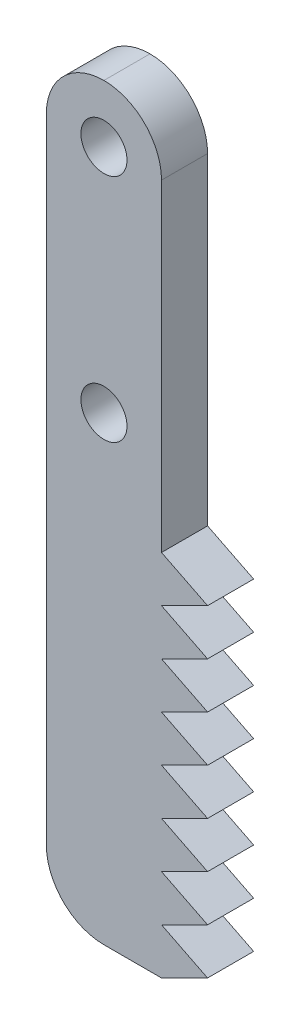
SolidWorks part; units mm, degrees
ref_plane "Plan de face" through (0, 0, 0) normal (0, 0, 1) x (1, 0, 0)
ref_plane "Plan de dessus" through (0, 0, 0) normal (0, 1, 0) x (1, 0, 0)
ref_plane "Plan de droite" through (0, 0, 0) normal (1, 0, 0) x (0, 0, -1)
sketch "Esquisse1" plane through (0, 0, 0) normal (0, 0, 1) x (1, 0, 0)
  line L0 (-25, 162.5) -> (25, -162.5) construction
  line L1 (-25, 162.5) -> (25, 162.5)
  line L2 (-25, 162.5) -> (-25, -162.5)
  line L3 (-25, -162.5) -> (25, -162.5)
  line L4 (25, 162.5) -> (25, -162.5)
  line L5 (25, -162.5) -> (45, -152.5)
  line L6 (45, -152.5) -> (25, -142.5)
  line L7 (25, -142.5) -> (45, -132.5)
  line L8 (45, -132.5) -> (25, -122.5)
  line L9 (25, -122.5) -> (45, -112.5)
  line L10 (45, -112.5) -> (25, -102.5)
  line L11 (25, -102.5) -> (45, -92.5)
  line L12 (45, -92.5) -> (25, -82.5)
  line L13 (25, -82.5) -> (45, -72.5)
  line L14 (45, -72.5) -> (25, -62.5)
  line L15 (25, -62.5) -> (45, -52.5)
  line L16 (45, -52.5) -> (25, -42.5)
  line L17 (25, -42.5) -> (45, -32.5)
  line L18 (45, -32.5) -> (25, -22.5)
  line L19 (25, -22.5) -> (45, -12.5)
  line L20 (45, -12.5) -> (25, -2.5)
  circle A0 centre (0, 137.5) radius 10
  circle A1 centre (0, 37.5) radius 10
  dimension "D2" = 20
  dimension "D4" = 20
  dimension "D1" = 50
  dimension "D3" = 25
  dimension "D5" = 100
  dimension "D6" = 20
  dimension "D7" = 20
  dimension "D9" = 40
  dimension "D8" = 8
extrude "Boss.-Extru.1" add sketch "Esquisse1" along normal blind 20 contours L0 L2 L3 A1 | L1 L0 A1 L4 A0 | L19 L20 L4 | L17 L18 L4 | L15 L16 L4 | L13 L14 L4 | L11 L12 L4 | L9 L10 L4 | L7 L8 L4 | L5 L6 L4 region at (8.9241, 51.2743, 0) region at (-8.3392, -54.7223, 0) region at (31.6667, -12.5, 0) region at (31.6667, -152.5, 0) region at (31.6667, -32.5, 0) region at (31.6667, -132.5, 0) region at (31.6667, -52.5, 0) region at (31.6667, -112.5, 0) region at (31.6667, -72.5, 0) region at (31.6667, -92.5, 0)
fillet "Congé1" radius 25 3 edges at (-25, -162.5, 10) (25, 162.5, 10) (-25, 162.5, 10)
